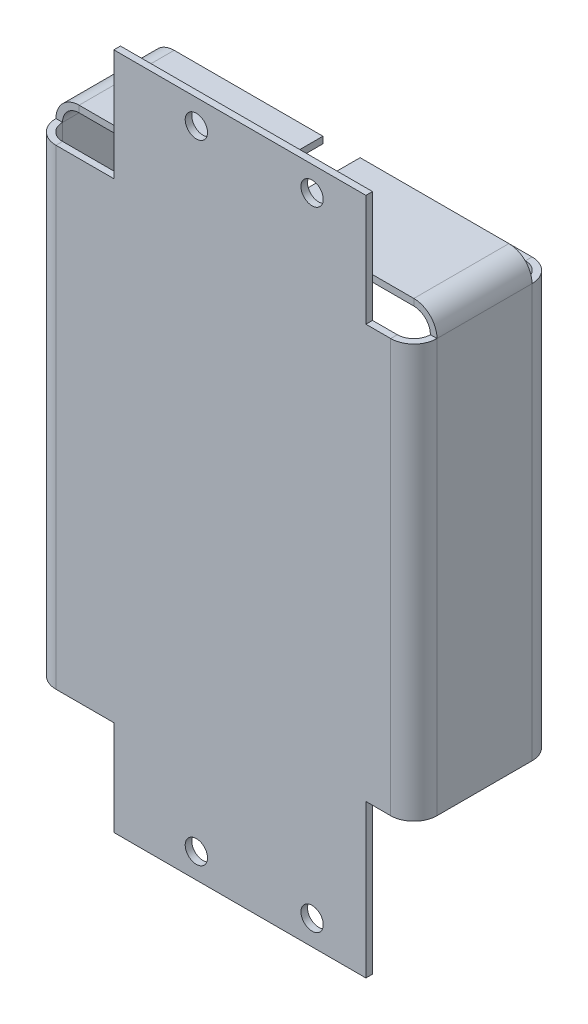
SolidWorks part; units mm, degrees
note: The reader was unsure of these and kept them because the rebuilt part matched: flange length of "Edge-Flange1", "Edge-Flange4", "Edge-Flange5".
ref_plane "Front Plane" through (0, 0, 0) normal (0, 0, 1) x (1, 0, 0)
ref_plane "Top Plane" through (0, 0, 0) normal (0, 1, 0) x (1, 0, 0)
ref_plane "Right Plane" through (0, 0, 0) normal (1, 0, 0) x (0, 0, -1)
sketch "Sketch1" plane through (0, 0, 0) normal (0, 0, 1) x (1, 0, 0)
  line L0 (16.75, 0) -> (16.75, -18.5)
  line L1 (21.75, 50) -> (16.75, 50)
  line L2 (21.75, 50) -> (21.75, 0)
  line L3 (21.75, 0) -> (16.75, 0)
  line L4 (-22.75, 50) -> (-22.75, -7)
  line L5 (16.75, -18.5) -> (-13.75, -18.5)
  line L6 (-13.75, -18.5) -> (-13.75, -7)
  line L7 (16.75, 50) -> (16.75, 63.5)
  line L9 (16.75, 63.5) -> (-13.75, 63.5)
  line L10 (-13.75, 63.5) -> (-13.75, 50)
  line L11 (-13.75, -7) -> (-22.75, -7)
  line L12 (-13.75, 50) -> (-22.75, 50)
  circle A0 centre (10.2378, -15.5) radius 1.35
  circle A1 centre (-3.7622, -15.5) radius 1.35
  circle A2 centre (10.2378, 60.5) radius 1.35
  circle A3 centre (-3.7622, 60.5) radius 1.35
  dimension "D6" = 6.5122
  dimension "D7" = 3
  dimension "D8" = 2.7
  dimension "D9" = 3
  dimension "D10" = 14
  dimension "D11" = 76
  dimension "D12" = 14
  dimension "D13" = 3
  dimension "D14" = 3
  dimension "D1" = 50
  dimension "D2" = 9
  dimension "D3" = 82
  dimension "D4" = 13.5
  dimension "D5" = 30.5
  dimension "D15" = 11.5
  dimension "D16" = 5
sheet metal parameters "Sheet-Metal1" thickness 0.8 parameters "D1"=2
base flange "Base-Flange1" sketch "Sketch1" thickness 0.8 reverse thickness direction yes parameters "D1"=2
edge flange "Edge-Flange1" sketch "Sketch6" flange profiles "Sketch6", "Sketch11" flange angle 90 flange length 13.5 flange position material outside bend radius 2 thickness 0.8 parameters "D6"=10, "D8"=1
sketch "Sketch6" plane through (21.75, 0, 0) normal (-1, 0, 0) x (0, 1, 0)
  line L2 (0, 0) -> (0, 13.5)
  line L3 (0, 13.5) -> (50, 13.5)
  line L4 (50, 13.5) -> (50, 0)
  line L6 (50, 0) -> (0, 0) construction
  line L7 (50, 0) -> (0, 0)
sketch "Sketch11" plane through (-22.75, 0, 0) normal (1, 0, 0) x (0, -1, 0)
  line L0 (7, 0) -> (-50, 0) construction
  line L1 (7, 0) -> (-50, 0)
  line L2 (7, 0) -> (7, 13.5)
  line L3 (7, 13.5) -> (-50, 13.5)
  line L4 (-50, 13.5) -> (-50, 0)
bend "EdgeBend1" bend radius 2 bend angle 90 parameters "D5"=1
bend "EdgeBend3" bend radius 2 bend angle 90 parameters "D5"=2
edge flange "Edge-Flange4" sketch "Sketch19" flange profiles "Sketch19", "Sketch20" flange angle 90 flange length 20 flange position bend outside bend radius 2 thickness 0.8 parameters "D6"=10, "D8"=1
sketch "Sketch19" plane through (21.75, 50, 0) normal (0, -1, 0) x (0, 0, 1)
  line L2 (-13.5, 0) -> (-13.5, 20)
  line L3 (-13.5, 20) -> (-2, 20)
  line L4 (-2, 20) -> (-2, 0)
  line L6 (-2, 0) -> (-13.5, 0) construction
  line L7 (-2, 0) -> (-13.5, 0)
sketch "Sketch20" plane through (-22.75, 50, 0) normal (0, -1, 0) x (0, 0, -1)
  line L0 (13.5, 0) -> (2, 0) construction
  line L1 (13.5, 0) -> (2, 0)
  line L2 (13.5, 0) -> (13.5, 20)
  line L3 (13.5, 20) -> (2, 20)
  line L4 (2, 20) -> (2, 0)
bend "EdgeBend5" bend radius 2 bend angle 90 parameters "D5"=3
bend "EdgeBend6" bend radius 2 bend angle 90 parameters "D5"=4
edge flange "Edge-Flange5" sketch "Sketch28" flange profiles "Sketch28", "Sketch29" flange angle 90 flange length 10 flange position bend outside bend radius 2 thickness 0.8 parameters "D6"=10, "D8"=1
sketch "Sketch28" plane through (21.75, 0, -13.5) normal (0, 0, 1) x (0, 1, 0)
  line L1 (50, 0) -> (0, 0) construction
  line L2 (0, 0) -> (0, 10)
  line L3 (0, 10) -> (50, 10)
  line L4 (50, 10) -> (50, 0)
  line L5 (50, 0) -> (0, 0)
sketch "Sketch29" plane through (-22.75, 0, -13.5) normal (0, 0, 1) x (0, -1, 0)
  line L0 (7, 0) -> (-50, 0) construction
  line L1 (7, 0) -> (-50, 0)
  line L2 (7, 0) -> (7, 10)
  line L3 (7, 10) -> (-50, 10)
  line L4 (-50, 10) -> (-50, 0)
bend "EdgeBend7" bend radius 2 bend angle 90 parameters "D5"=5
bend "EdgeBend8" bend radius 2 bend angle 90 parameters "D5"=6
flat pattern "Flat-Pattern1" [suppressed]
sketch "Bend-Lines1" plane through (0, 0, 0.8) normal (0, 0, 1) x (1, 0, 0)
  line L0 (-22.6255, -7) -> (-22.6255, 50) construction
  line L1 (21.6255, 50) -> (21.6255, 0) construction
  line L2 (-22.6255, -7) -> (-22.6255, 50) construction
  line L3 (21.6255, 50) -> (21.6255, 0) construction
  line L4 (-36.0011, 51.8755) -> (-24.5011, 51.8755) construction
  line L5 (23.5011, 51.8755) -> (35.0011, 51.8755) construction
  line L6 (-36.0011, 51.8755) -> (-24.5011, 51.8755) construction
  line L7 (23.5011, 51.8755) -> (35.0011, 51.8755) construction
  line L8 (-37.8766, -7) -> (-37.8766, 50) construction
  line L9 (36.8766, 50) -> (36.8766, 0) construction
  line L10 (-37.8766, -7) -> (-37.8766, 50) construction
  line L11 (36.8766, 50) -> (36.8766, 0) construction
sketch3d "Bounding-Box1" [suppressed]
  line L0 (-69.5021, -18.5, 0) -> (25.0021, -18.5, 0) construction
  line L1 (-69.5021, 71.7511, 0) -> (25.0021, 71.7511, 0) construction
  line L2 (-69.5021, -18.5, 0) -> (-69.5021, 71.7511, 0) construction
  line L3 (25.0021, -18.5, 0) -> (25.0021, 71.7511, 0) construction
bend of the flat pattern "Flatten-<EdgeBend1>1"
bend of the flat pattern "Flatten-<EdgeBend3>1"
bend of the flat pattern "Flatten-<EdgeBend5>1"
bend of the flat pattern "Flatten-<EdgeBend6>1"
bend of the flat pattern "Flatten-<EdgeBend7>1"
bend of the flat pattern "Flatten-<EdgeBend8>1"
fillet "Fillet1" [suppressed] radius 2
fillet "Fillet2" [suppressed] radius 1.88
